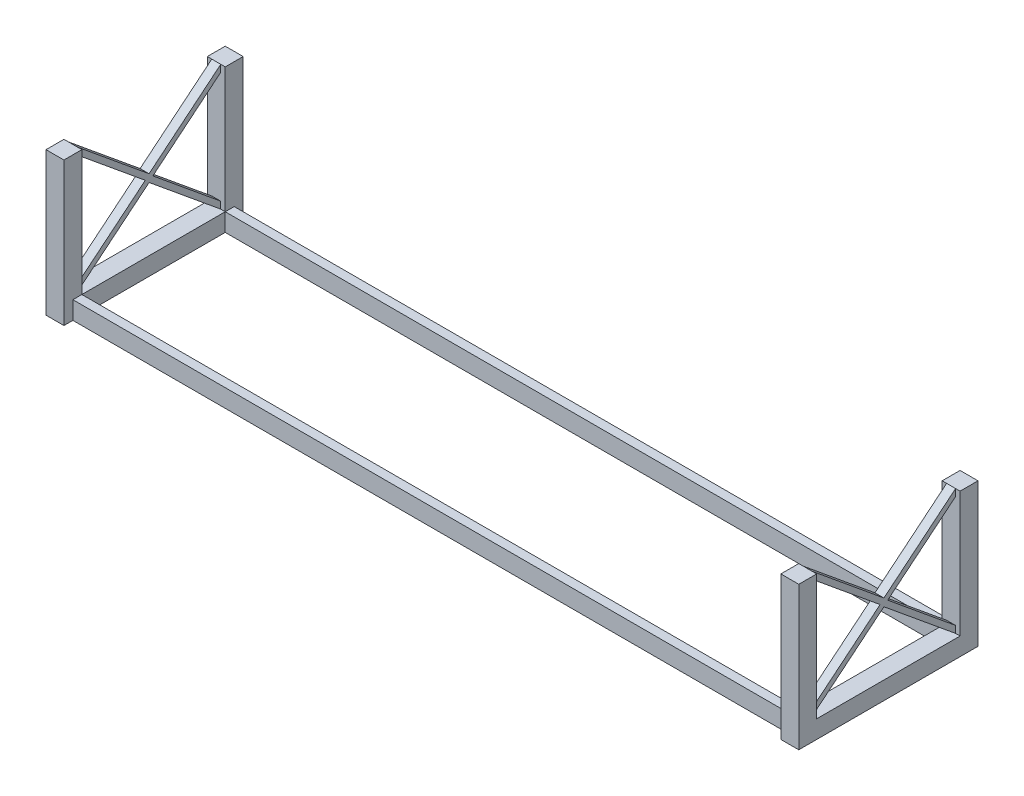
SolidWorks part; units mm, degrees
ref_plane "Płaszczyzna przednia" through (0, 0, 0) normal (0, 0, 1) x (1, 0, 0)
ref_plane "Płaszczyzna górna" through (0, 0, 0) normal (0, 1, 0) x (1, 0, 0)
ref_plane "Płaszczyzna prawa" through (0, 0, 0) normal (1, 0, 0) x (0, 0, -1)
sketch "Sketch1" plane through (0, 0, 0) normal (1, 0, 0) x (0, 0, -1)
  line L0 (-50, 0) -> (-50, 80)
  line L1 (-50, 80) -> (-40, 80)
  line L2 (-40, 80) -> (-40, 10)
  line L3 (-40, 10) -> (40, 10)
  line L7 (50, 0) -> (-50, 0)
  line L8 (0, 10) -> (0, 80) construction
  line L10 (-40, 80) -> (40, 80) construction
  line L12 (0, 45) -> (0, 47.1213)
  line L13 (0, 45) -> (0, 42.8787)
  line L14 (0, 47.1213) -> (-40, 80)
  line L15 (0, 42.8787) -> (-40, 10)
  line L16 (2.1213, 45) -> (-2.1213, 45) construction
  line L17 (0, 47.1213) -> (-2.1213, 45) construction
  line L18 (-2.1213, 45) -> (-40, 76.135)
  line L19 (-2.1213, 45) -> (-40, 13.865)
  line L20 (0, 47.1213) -> (2.1213, 45) construction
  line L21 (2.1213, 45) -> (40, 13.865)
  line L22 (2.1213, 45) -> (40, 76.135)
  line L23 (0, 42.8787) -> (40, 10)
  line L24 (0, 47.1213) -> (40, 80)
  line L25 (40, 80) -> (40, 10)
  line L26 (50, 80) -> (40, 80)
  line L27 (50, 0) -> (50, 80)
  point P21 (0, 0)
  dimension "D1" = 10
  dimension "D2" = 4.2426
  dimension "D3" = 10
  dimension "D4" = 80
  dimension "D5" = 50
  dimension "D6" = 2.1213
  dimension "D7" = 45
  dimension "D8" = 2.9858
extrude "Boss-Extrude1" add sketch "Sketch1" along normal mid plane 10 contours L7 L27 L26 L25 L3 L2 L1 L0 region at (0, 40, 48.7194)
extrude "Boss-Extrude2" add sketch "Sketch1<4>" along normal mid plane 5 contours L18 L19 L2 L15 L13 L12 L14 | L25 L24 L12 L13 L23 L21 L22 region at (0, 62.9378, 20.5119) region at (0, 62.9378, -20.5119)
sketch "Sketch1<4>" plane through (0, 0, 0) normal (1, 0, 0) x (0, 0, -1) same geometry as "Sketch1"
sketch "Sketch2" plane through (0, 0, 0) normal (0, 1, 0) x (1, 0, 0)
  line L0 (5, 45) -> (205, 45)
  line L1 (5, 50) -> (5, 40) construction
  line L5 (0, 0) -> (122.3559, 0) construction
  line L6 (5, 45) -> (5, 40)
  line L7 (5, 40) -> (205, 40)
  line L8 (205, 40) -> (205, 45)
  line L9 (5, -40) -> (205, -40)
  line L10 (5, -45) -> (5, -40)
  line L11 (5, -45) -> (205, -45)
  line L12 (205, -40) -> (205, -45)
  dimension "D1" = 200
  dimension "D2" = 5
  dimension "D3" = 80
extrude "Boss-Extrude3" add sketch "Sketch2" along normal blind 10
mirror "Mirror1" about plane through (205, 10, 40) normal (-1, 0, 0) of bodies 104
